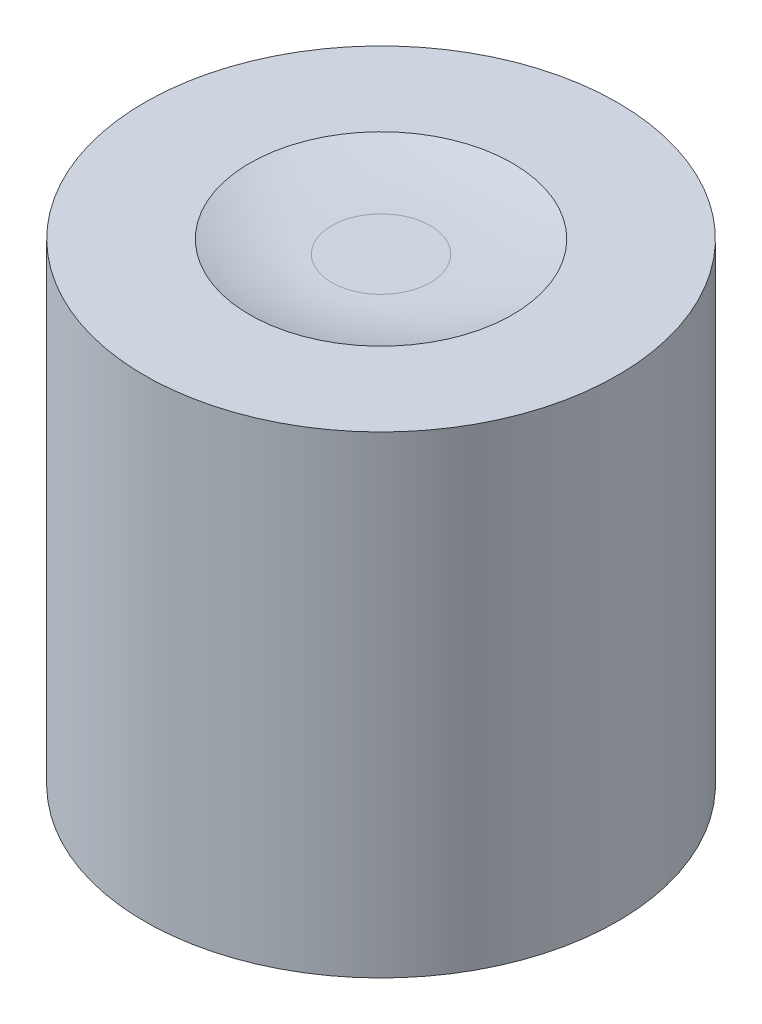
SolidWorks part; units mm, degrees
material "Brass"
ref_plane "Front Plane" through (0, 0, 0) normal (0, 0, 1) x (1, 0, 0)
ref_plane "Top Plane" through (0, 0, 0) normal (0, 1, 0) x (1, 0, 0)
ref_plane "Right Plane" through (0, 0, 0) normal (1, 0, 0) x (0, 0, -1)
sketch "Sketch1" plane through (0, 0, 0) normal (0, 0, 1) x (1, 0, 0)
  line L0 (4.5, 9) -> (0, 9)
  line L1 (0, 9) -> (0, 0)
  line L2 (0, 0) -> (4.5, 0)
  line L3 (4.5, 0) -> (4.5, 9)
  line L4 (0, 9) -> (0, 0) construction
revolve "Revolve1" add sketch "Sketch1" angle 360 about L4 reverse direction yes
sketch "Sketch2" plane through (0, 0, 0) normal (0, -1, 0) x (1, 0, 0)
  line L0 (0.5, -3.4641) -> (0.5, 3.4641)
  arc A0 (0.5, 3.4641) -> (0.5, -3.4641) centre (0, 0) cw
extrude "Boss-Extrude1" add sketch "Sketch2" along normal blind 0.25
sketch "Sketch3" plane through (0, 0, 0) normal (0, -1, 0) x (1, 0, 0)
  line L0 (-0.5, 3.4641) -> (-0.5, -3.4641)
  arc A0 (-0.5, -3.4641) -> (-0.5, 3.4641) centre (0, 0) cw
extrude "Boss-Extrude2" add sketch "Sketch3" along normal blind 0.25
sketch "Sketch4" plane through (0, 0, 0) normal (0, 0, 1) x (1, 0, 0)
  line L0 (2.5, 9) -> (0, 9)
  line L1 (0, 9) -> (0, 8.75)
  line L2 (0, 8.75) -> (0.9388, 8.75)
  line L3 (0, 9) -> (0, 8.75) construction
  arc A0 (0.9388, 8.75) -> (2.5, 9) centre (0.9388, 13.75) ccw
revolve "Cut-Revolve1" cut sketch "Sketch4" angle 360 about L3 reverse direction yes
sketch "Sketch5" plane through (0, 0, 0) normal (0, 0, 1) x (1, 0, 0)
  line L0 (2, 6) -> (0, 6)
  line L1 (0, 6) -> (0, -0.25)
  line L2 (0, -0.25) -> (2, -0.25)
  line L3 (2, -0.25) -> (2, 6)
  line L4 (0, 6) -> (0, -0.25) construction
revolve "Cut-Revolve2" cut sketch "Sketch5" angle 360 about L4 reverse direction yes
